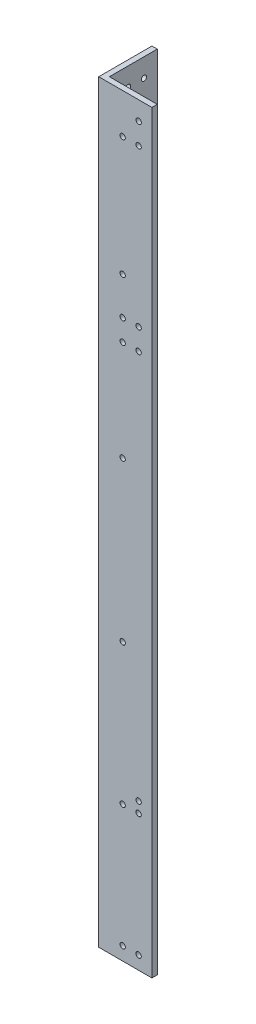
SolidWorks part; units mm, degrees
ref_plane "Front Plane" through (0, 0, 0) normal (0, 0, 1) x (1, 0, 0)
ref_plane "Top Plane" through (0, 0, 0) normal (0, 1, 0) x (1, 0, 0)
ref_plane "Right Plane" through (0, 0, 0) normal (1, 0, 0) x (0, 0, -1)
sketch "Sketch2" plane through (0, 0, 0) normal (0, 1, 0) x (1, 0, 0)
  line L0 (0, 31.75) -> (3.175, 31.75)
  line L1 (3.175, 31.75) -> (3.175, 3.175)
  line L2 (3.175, 3.175) -> (31.75, 3.175)
  line L3 (31.75, 3.175) -> (31.75, 0)
  line L4 (31.75, 0) -> (0, 0)
  line L5 (0, 0) -> (0, 31.75)
  point P9 (1.5875, 31.75)
  point P10 (31.75, 1.5875)
  dimension "D4" = 3.175
  dimension "D1" = 31.75
  dimension "D2" = 31.75
  dimension "D3" = 3.175
extrude "Boss-Extrude1" add sketch "Sketch2" along normal blind 450
sketch "RightSideHoles-Sketch3" plane through (0, 0, 0) normal (0, 0, 1) x (1, 0, 0)
  line L0 (0, 0) -> (31.75, 0) construction
  line L1 (0, 450) -> (31.75, 450) construction
  line L3 (0, 450) -> (0, 0) construction
  circle A0 centre (14.2875, 81.1125) radius 1.5875
  circle A1 centre (23.8125, 81.1125) radius 1.5875
  circle A3 centre (23.8125, 87.4625) radius 1.5875
  circle A5 centre (14.2875, 426.1875) radius 1.5875
  circle A6 centre (23.8125, 438.8875) radius 1.5875
  circle A7 centre (23.8125, 426.1875) radius 1.5875
  circle A8 centre (14.2875, 332.6026) radius 1.5875
  circle A9 centre (23.8125, 332.6026) radius 1.5875
  circle A10 centre (14.2875, 319.9026) radius 1.5875
  circle A11 centre (23.8125, 319.9026) radius 1.5875
  circle A12 centre (14.2875, 7.9375) radius 1.5875
  circle A13 centre (23.8125, 7.9375) radius 1.5875
  circle A14 centre (14.2875, 165) radius 1.5875
  circle A15 centre (14.2875, 260) radius 1.5875
  circle A16 centre (14.2875, 355) radius 1.5875
  dimension "D4" = 3.175
  dimension "D1" = 81.1125
  dimension "D2" = 14.2875
  dimension "D12" = 7.9375
  dimension "D7" = 12.7
  dimension "D3" = 9.525
  dimension "D10" = 332.6026
  dimension "D11" = 165
  dimension "D13" = 95
  dimension "D14" = 95
  dimension "D5" = 6.35
  dimension "D6" = 12.7
  dimension "D8" = 11.1125
sketch "FrontSideHoles-Sketch4" plane through (0, 0, 0) normal (-1, 0, 0) x (0, 0, 1)
  line L0 (-31.75, 450) -> (0, 450) construction
  line L1 (0, 450) -> (0, 0) construction
  line L3 (-31.75, 0) -> (0, 0) construction
  circle A0 centre (-23.8125, 81.1125) radius 1.5875
  circle A2 centre (-23.8125, 87.4625) radius 1.5875
  circle A3 centre (-14.2875, 87.4625) radius 1.5875
  circle A4 centre (-23.8125, 438.8875) radius 1.5875
  circle A5 centre (-14.2875, 438.8875) radius 1.5875
  circle A6 centre (-23.8125, 426.1875) radius 1.5875
  circle A8 centre (-14.2875, 338.1776) radius 1.5875
  circle A9 centre (-14.2875, 319.6526) radius 1.5875
  circle A10 centre (-14.2875, 165) radius 1.5875
  circle A11 centre (-14.2875, 260) radius 1.5875
  circle A12 centre (-14.2875, 355) radius 1.5875
  circle A13 centre (-23.8125, 7.9375) radius 1.5875
  circle A14 centre (-14.2875, 7.9375) radius 1.5875
  dimension "D4" = 3.175
  dimension "D7" = 12.7
  dimension "D13" = 95
  dimension "D14" = 95
  dimension "D5" = 6.35
  dimension "D6" = 11.1125
  dimension "D9" = 18.525
  dimension "D10" = 14.2875
  dimension "D8" = 319.6526
  dimension "D12" = 165
  dimension "D15" = 7.9375
  dimension "D2" = 14.2875
  dimension "D11" = 9.525
  dimension "D3" = 81.1125
extrude "RightSideHoles-Cut-Extrude1" cut sketch "RightSideHoles-Sketch3" against normal blind 3.175
extrude "FrontSideHoles-Cut-Extrude2" cut sketch "FrontSideHoles-Sketch4" against normal blind 3.175
equation "\"RailThickness\"= .125in'Spec"
equation "\"VSWidth\"= 1.25in'Spec"
equation "\"VSHeight\"= 1.25in'Spec"
equation "\"VSLength\"= 450mm"
equation "\"HoleOffsetFromEdge\"= \"RailThickness\" * 2.5"
equation "\"HoleOffsetFromSide\"= \"RailThickness\" * 3.5"
equation "\"LegHeight\"= 70mm'Space needed for PSU/Stepper/Electronics"
equation "\"VSBottomSideRailHoleY1FromBottomOfLowerRail\"= \"V1 BottomOfLowerRail\" + \"HoleOffsetFromSide\"'Equals 70.1125"
equation "\"VSSideRailHoleX1FromSide\"= \"HoleOffsetFromSide\" + \"RailThickness\""
equation "\"FasteningHoleDiameter\"= .125in"
equation "\"VSBottomSideRailHoleY2FromY1\"= \"LowerRailHeight\" - \"HoleOffsetFromSide\" - \"HoleOffsetFromEdge\"'Equals 6.35"
equation "\"VSTopSideRailHoleY1FromEdge\"= \"HoleOffsetFromEdge\" + \"RailThickness\""
equation "\"D4@RightSideHoles-Sketch3\" = \"FasteningHoleDiameter\""
equation "\"D1@RightSideHoles-Sketch3\" = \"VSBottomSideRailHoleY1FromBottomOfLowerRail\""
equation "\"D2@RightSideHoles-Sketch3\" = \"VSSideRailHoleX1FromSide\""
equation "\"D1@Boss-Extrude1\"=\"VSLength\""
equation "\"D4@FrontSideHoles-Sketch4\" = \"FasteningHoleDiameter\""
equation "\"D6@FrontSideHoles-Sketch4\" = \"VSTopSideRailHoleY1FromEdge\""
equation "\"VSMidSideRailHoleY1FromV8TopOfMidSideRail\"= \"V8 ToTopOfMidSideRail\" - \"HoleOffsetFromEdge\"'Equals 308.2875"
equation "\"LowerRailHeight\"= 1.00in"
equation "\"D2@Sketch2\"=\"VSWidth\""
equation "\"D1@Sketch2\"=\"VSHeight\""
equation "\"TopRailHeight\"= 1.25in"
equation "\"MidSideRailHeight\"= 1.25in"
equation "\"D12@RightSideHoles-Sketch3\"=\"HoleOffsetFromEdge\""
equation "\"VSMidSideRailHoleY2FromY1\"= \"MidSideRailHeight\" - \"HoleOffsetFromSide\" - \"HoleOffsetFromEdge\"'Equals 12.7"
equation "\"D7@RightSideHoles-Sketch3\"=\"VSMidSideRailHoleY2FromY1\""
equation "\"VSTopSideRailHoleY2FromY1\"= \"TopRailHeight\" - \"VSTopSideRailHoleY1FromEdge\" - \"HoleOffsetFromEdge\"'Equals 12.7"
equation "\"D7@FrontSideHoles-Sketch4\"=\"VSTopSideRailHoleY2FromY1\""
equation "\"VSSideRailHoleX2FromX1\"= \"VSWidth\" - \"VSSideRailHoleX1FromSide\" - \"HoleOffsetFromEdge\""
equation "\"D3@RightSideHoles-Sketch3\"=\"VSSideRailHoleX2FromX1\""
equation "\"1mmSpacer\"= 1mm"
equation "\"20TGT2PulleyWidth\"= 8.7mm'The STL of the Pulley in the diagram is a bit larger"
equation "\"BeltTensionerUpperLowerWallThickness\"= 7mm"
equation "\"BeltTensionerInnerHeight\"= \"20TGT2PulleyWidth\" * 2 + \"1mmSpacer\" * 3"
equation "\"BeltTensionerHeight\"= \"BeltTensionerInnerHeight\" + \"BeltTensionerUpperLowerWallThickness\" * 2"
equation "\"D9@FrontSideHoles-Sketch4\"=\"VSBeltTensionerHoleY2FromY1\""
equation "\"VSBeltTensionerHoleY1FromBottom\"= \"V9 FromBottomGantryPulleyToBottomOfBeltTensioner\" + \"HoleOffsetFromEdge\""
equation "\"VSBeltTensionerHoleY2FromY1\"= \"BeltTensionerHeight\" - \"HoleOffsetFromEdge\" * 2"
equation "\"V1 BottomOfLowerRail\"= \"LegHeight\""
equation "\"StepperShaftLength\"= 24mm'Pulley will be attached to the end"
equation "\"ZAxisLeadScrewLength\"= 200mm"
equation "\"LM8UUHeight\"= 24mm'Spec"
equation "\"V2 ToBedAtTopOfZAxis\"= \"V1 BottomOfLowerRail\" + \"StepperShaftLength\" + \"ZAxisLeadScrewLength\" - \"LM8UUHeight\" / 2"
equation "\"HotEndToTopOfXAxisGB\"= 63.315144mm'Measured from the100.Should be 63.315144"
equation "\"TopOfGBToBottomOfLinearRail\"= \"LinearGBWidth\" / 2 + \"LinearRailWidth\" / 2"
equation "\"LinearGBWidth\"= 27mm'Spec"
equation "\"V5 ToBottomOfXAxisLinearRail\"= \"V4 ToTopOfBuildPlate/HotEndTip\" + \"HotEndToTopOfXAxisGB\" - \"TopOfGBToBottomOfLinearRail\""
equation "\"LinearRailWidth\"= 12mm'Spec"
equation "\"V6 ToBottomOfGantryPulley\"= \"V5 ToBottomOfXAxisLinearRail\" - \"DistanceFromGABTopToLowerPulley\""
equation "\"GABUpperHeight\"= 6mm"
equation "\"GABMidWallHeight\"= 28mm'Must equal 28 or changes alignment"
equation "\"GABMidShortRiserHeight\"= \"GABMidWallHeight\" / 2 - \"20TGT2PulleyWidth\"'Equals 5.3"
equation "\"GABRiserBossOffset\"= 0.8mm'Aligns Pulleys"
equation "\"DistanceFromGABTopToLowerPulley\"= \"GABUpperHeight\" + \"GABMidWallHeight\" - \"GABMidShortRiserHeight\" + \"GABRiserBossOffset\" / 2"
equation "\"V7 ToTopOfMidBackRail\"= \"V6 ToBottomOfGantryPulley\" + \"StepperShaftLength\""
equation "\"D10@RightSideHoles-Sketch3\"=\"VSMidSideRailHoleY1FromV8TopOfMidSideRail\""
equation "\"BedToBuildPlateStandoffLength\"= 15mm"
equation "\"BuildPlateHeight\"= 8mm'Spec"
equation "\"V4 ToTopOfBuildPlate/HotEndTip\"= \"V2 ToBedAtTopOfZAxis\" + \"BedToBuildPlateStandoffLength\" + \"BuildPlateHeight\""
equation "\"D8@FrontSideHoles-Sketch4\"=\"VSBeltTensionerHoleY1FromBottom\""
equation "\"V8 ToTopOfMidSideRail\"= \"V7 ToTopOfMidBackRail\" - \"RailThickness\""
equation "\"V9 FromBottomGantryPulleyToBottomOfBeltTensioner\"= \"V6 ToBottomOfGantryPulley\" - \"BeltTensionerUpperLowerWallThickness\" - \"1mmSpacer\""
equation "\"BeltTensionerMountingHoleOffsetFromEdge\"= \"HoleOffsetFromEdge\""
equation "\"VSBeltTensionerXMountingHoleOffsetFromSide\"= \"BeltTensionerMountingHoleOffsetFromEdge\" + \"RailThickness\" * 2"
equation "\"D10@FrontSideHoles-Sketch4\"=\"VSBeltTensionerXMountingHoleOffsetFromSide\""
equation "\"VSEnclosureOffsets\"= ( \"VSLength\" - \"LegHeight\" ) / 4"
equation "\"D11@RightSideHoles-Sketch3\"=\"LegHeight\" + \"VSEnclosureOffsets\""
equation "\"D13@RightSideHoles-Sketch3\"=\"VSEnclosureOffsets\""
equation "\"D14@RightSideHoles-Sketch3\"=\"VSEnclosureOffsets\""
equation "\"D12@FrontSideHoles-Sketch4\"= \"LegHeight\" + \"VSEnclosureOffsets\""
equation "\"D13@FrontSideHoles-Sketch4\"=\"VSEnclosureOffsets\""
equation "\"D14@FrontSideHoles-Sketch4\"=\"VSEnclosureOffsets\""
equation "\"D15@FrontSideHoles-Sketch4\"=\"HoleOffsetFromEdge\""
equation "\"D2@FrontSideHoles-Sketch4\"=\"VSSideRailHoleX1FromSide\""
equation "\"D5@FrontSideHoles-Sketch4\"=\"VSBottomSideRailHoleY2FromY1\""
equation "\"D3@FrontSideHoles-Sketch4\"=\"VSBottomSideRailHoleY1FromBottomOfLowerRail\""
equation "\"D5@RightSideHoles-Sketch3\"=\"VSBottomSideRailHoleY2FromY1\""
equation "\"D6@RightSideHoles-Sketch3\"=\"VSTopSideRailHoleY2FromY1\""
equation "\"D8@RightSideHoles-Sketch3\"=\"VSTopSideRailHoleY1FromEdge\""
